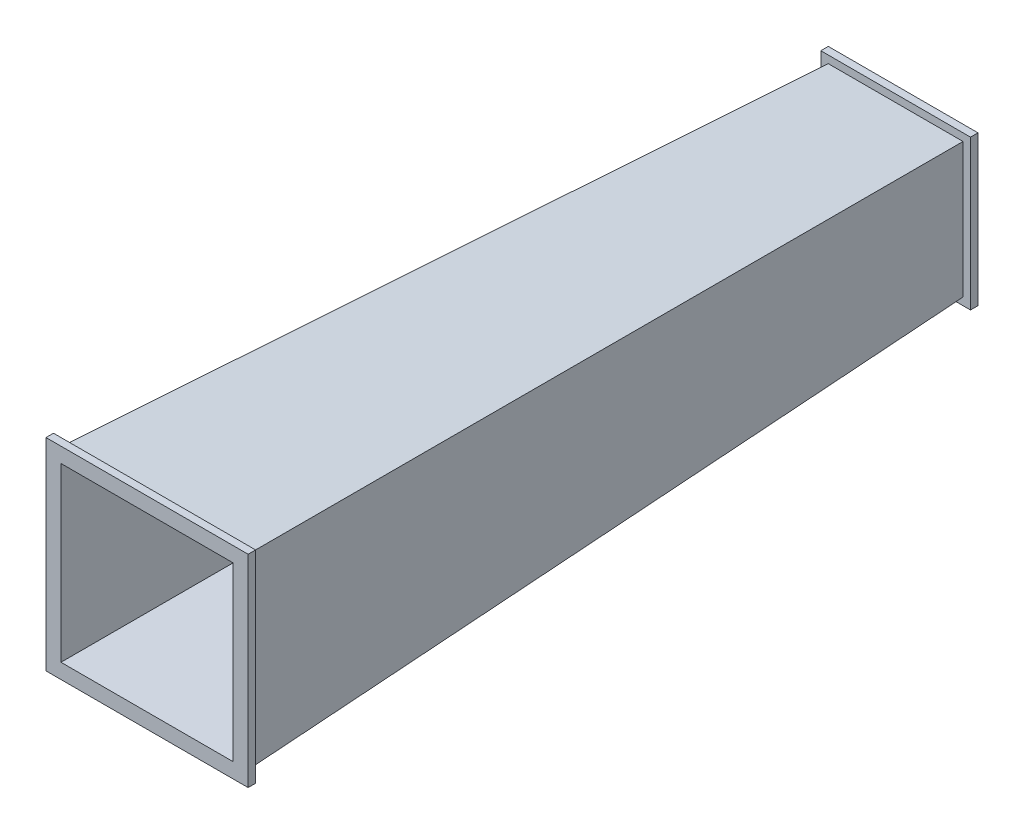
SolidWorks part; units mm, degrees
ref_plane "Front Plane" through (0, 0, 0) normal (0, 0, 1) x (1, 0, 0)
ref_plane "Top Plane" through (0, 0, 0) normal (0, 1, 0) x (1, 0, 0)
ref_plane "Right Plane" through (0, 0, 0) normal (1, 0, 0) x (0, 0, -1)
sketch "Sketch1" plane through (0, 0, 0) normal (0, 0, 1) x (1, 0, 0)
  line L1 (-45, 45) -> (45, 45)
  line L2 (-45, 45) -> (-45, -45)
  line L3 (-45, -45) -> (45, -45)
  line L4 (45, 45) -> (45, -45)
  line L5 (-45, 45) -> (45, -45) construction
  line L6 (-45, -45) -> (45, 45) construction
  point P0 (0, 0)
  dimension "D1" = 90
  dimension "D2" = 90
ref_plane "Plane1" through (0, 0, 500) normal (0, 0, 1) x (1, 0, 0)
sketch "Sketch4" plane through (0, 0, 500) normal (0, 0, 1) x (1, 0, 0)
  line L1 (-62.5, 62.5) -> (62.5, 62.5)
  line L2 (-62.5, 62.5) -> (-62.5, -62.5)
  line L3 (-62.5, -62.5) -> (62.5, -62.5)
  line L4 (62.5, 62.5) -> (62.5, -62.5)
  line L5 (-62.5, 62.5) -> (62.5, -62.5) construction
  line L6 (-62.5, -62.5) -> (62.5, 62.5) construction
  point P0 (0, 0)
loft "Loft2" add profiles "Sketch4", "Sketch1" connector at (62.5, 62.5, 500) connector at (45, 45, 0)
shell "Shell2" thickness 5 removed face at (0, 0, 0) removed face at (0, 0, 500)
sketch "Sketch5" plane through (0, 0, 0) normal (0, 0, -1) x (-1, 0, 0)
  line L4 (50, 50) -> (-50, 50)
  line L5 (-50, 50) -> (-50, -50)
  line L6 (-50, -50) -> (50, -50)
  line L7 (50, -50) -> (50, 50)
  line L8 (-45, 45) -> (-45, -45)
  line L9 (-45, -45) -> (45, -45)
  line L10 (45, -45) -> (45, 45)
  line L11 (45, 45) -> (-45, 45)
  line L12 (-45, 45) -> (-45, -45)
  line L13 (-45, -45) -> (45, -45)
  line L14 (45, -45) -> (45, 45)
  line L15 (45, 45) -> (-45, 45)
  dimension "D1" = 0
  dimension "D2" = 5
extrude "Boss-Extrude1" add sketch "Sketch5" along normal blind 5 separate body
sketch "Sketch6" plane through (0, 0, 500) normal (0, 0, 1) x (1, 0, 0)
  line L0 (67.5, 67.5) -> (-67.5, 67.5)
  line L1 (-67.5, 67.5) -> (-67.5, -67.5)
  line L2 (-67.5, -67.5) -> (67.5, -67.5)
  line L3 (67.5, -67.5) -> (67.5, 67.5)
  line L4 (62.5, -62.5) -> (62.5, 62.5)
  line L5 (62.5, 62.5) -> (-62.5, 62.5)
  line L6 (-62.5, 62.5) -> (-62.5, -62.5)
  line L7 (-62.5, -62.5) -> (62.5, -62.5)
  line L8 (62.5, -62.5) -> (62.5, 62.5)
  line L9 (62.5, 62.5) -> (-62.5, 62.5)
  line L10 (-62.5, 62.5) -> (-62.5, -62.5)
  line L11 (-62.5, -62.5) -> (62.5, -62.5)
  line M5 (57.4969, 57.4969) -> (57.4969, -57.4969)
  line M6 (57.4969, -57.4969) -> (-57.4969, -57.4969)
  line M7 (-57.4969, -57.4969) -> (-57.4969, 57.4969)
  line M8 (-57.4969, 57.4969) -> (57.4969, 57.4969)
  dimension "D1" = 0
  dimension "D2" = 5
extrude "Boss-Extrude2" add sketch "Sketch6" against normal blind 5 contours L2 L3 L0 L1 | M8 M5 M6 M7 region at (65.5908, 0, 500) region at (0, -60.7322, 500)
